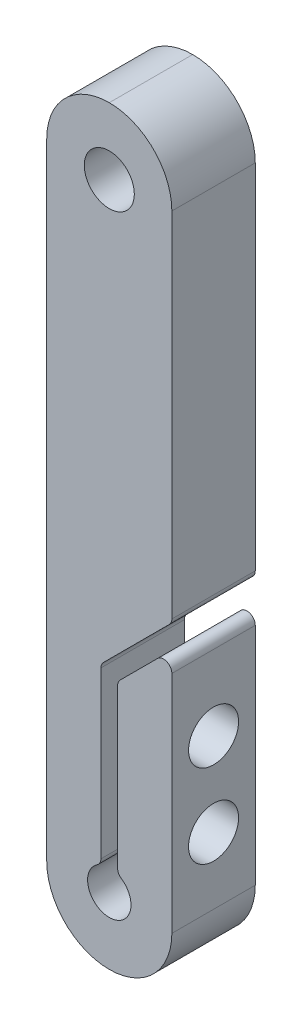
SolidWorks part; units mm, degrees
ref_plane "Front" through (0, 0, 0) normal (0, 0, 1) x (1, 0, 0)
ref_plane "Top" through (0, 0, 0) normal (0, 1, 0) x (1, 0, 0)
ref_plane "Right" through (0, 0, 0) normal (1, 0, 0) x (0, 0, -1)
sketch "Esquisse1" plane through (0, 0, 0) normal (0, 0, 1) x (1, 0, 0)
  line L1 (0, 0) -> (15, 0)
  line L2 (0, 0) -> (0, 90)
  line L3 (0, 90) -> (15, 90)
  line L4 (15, 0) -> (15, 90)
  dimension "D1" = 15
  dimension "D2" = 90
extrude "Boss.-Extru.1" add sketch "Esquisse1" along normal blind 10
sketch "Esquisse2" plane through (0, 0, 10) normal (0, 0, 1) x (1, 0, 0)
  line L0 (7.5, 90) -> (7.5, 81) construction
  line L1 (15, 90) -> (0, 90) construction
  line L2 (0, 0) -> (15, 0) construction
  line L3 (7.5, 8) -> (7.5, 0) construction
  circle A1 centre (7.5, 82) radius 3
  circle A2 centre (7.5, 8) radius 2.6
  point P11 (7.5, 0)
  dimension "D2" = 8
  dimension "D3" = 6
  dimension "D4" = 5.2
  dimension "D5" = 8
extrude "Enlèv. mat.-Extru.1" cut sketch "Esquisse2" against normal up to vertex (10 mm away) up to point (0, 90, 0)
fillet "Congé1" radius 7.5 4 edges at (15, 90, 5) (0, 90, 5) (15, 0, 5) (0, 0, 5)
sketch "Esquisse3" plane through (0, 0, 10) normal (0, 0, 1) x (1, 0, 0)
  line L0 (6.5, 10.4) -> (6.5, 31.2284)
  line L1 (6.5, 31.2284) -> (15, 39.7284)
  line L2 (15, 7.5) -> (15, 82.5) construction
  line L3 (15, 39.7284) -> (15, 36.9)
  line L4 (15, 36.9) -> (8.5, 30.4)
  line L5 (8.5, 30.4) -> (8.5, 10.4)
  line L6 (8.5, 10.4) -> (6.5, 10.4)
  line L7 (7.5, 10.6) -> (7.5, 10.4) construction
  circle A0 centre (7.5, 8) radius 2.6 construction
  dimension "D1" = 2
  dimension "D2" = 2
  dimension "D3" = 20
  dimension "D4" = 135
extrude "Enlèv. mat.-Extru.2" cut sketch "Esquisse3" against normal through all
sketch "Esquisse4" plane through (15, 0, 0) normal (1, 0, 0) x (0, 0, -1)
  line L0 (-5, 7.5) -> (-5, 36.9) construction
  line L1 (-10, 7.5) -> (0, 7.5) construction
  line L2 (0, 36.9) -> (-10, 36.9) construction
  circle A0 centre (-5, 15.5) radius 2.1
  circle A1 centre (-5, 25.5) radius 2.1
  dimension "D1" = 10
  dimension "D2" = 4.2
  dimension "D3" = 8
extrude "Enlèv. mat.-Extru.3" cut sketch "Esquisse4" against normal through all
sketch "Esquisse5" plane through (15, 0, 0) normal (1, 0, 0) x (0, 0, -1)
  circle A0 centre (-5, 25.5) radius 3
  circle A1 centre (-5, 15.5) radius 3
  dimension "D1" = 6
extrude "Enlèv. mat.-Extru.4" cut sketch "Esquisse5" against normal up to vertex (6.5 mm away) up to point (8.5, 30.4, 0)
fillet "Congé2" radius 1 6 edges at (15, 36.9, 5) (8.5, 10.4, 5) (6.5, 10.4, 5) (8.5, 30.4, 5) (15, 39.7284, 5) (6.5, 31.2284, 5)
